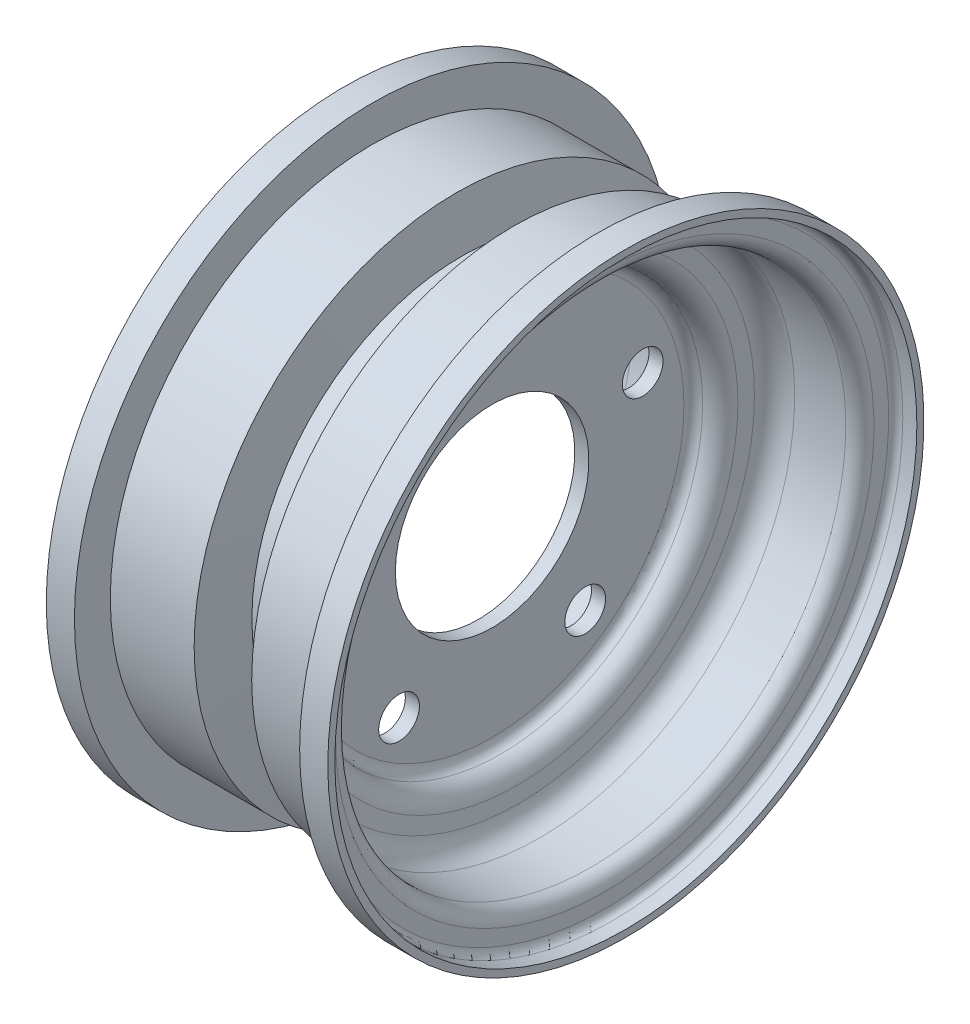
SolidWorks part; units mm, degrees
material "1023 Carbon Steel Sheet (SS)"
ref_plane "Front Plane" through (0, 0, 0) normal (0, 0, 1) x (1, 0, 0)
ref_plane "Top Plane" through (0, 0, 0) normal (0, 1, 0) x (1, 0, 0)
ref_plane "Right Plane" through (0, 0, 0) normal (1, 0, 0) x (0, 0, -1)
sketch "Sketch2" plane through (0, 0, 0) normal (0, 0, 1) x (1, 0, 0)
  line L0 (2.54, 0) -> (2.54, 34.925) construction
  line L1 (2.54, 34.925) -> (2.54, 73.025)
  line L2 (2.54, 73.025) -> (10.922, 73.025)
  line L3 (50.8, 107.569) -> (50.8, 105.029)
  line L4 (12.7, 92.075) -> (43.18, 92.075)
  line L5 (43.18, 92.075) -> (43.18, 105.029)
  line L6 (43.18, 105.029) -> (50.8, 105.029)
  line L7 (10.922, 73.025) -> (12.7, 92.075)
  line L8 (0, 0) -> (2.54, 0) construction
  line L9 (0, 0) -> (0, 213.5492) construction
  line L10 (0, 34.925) -> (0, 75.565)
  line L11 (0, 75.565) -> (8.608, 75.565)
  line L12 (8.608, 75.565) -> (10.386, 94.615)
  line L13 (10.386, 94.615) -> (40.64, 94.615)
  line L14 (40.64, 94.615) -> (40.64, 107.569)
  line L15 (40.64, 107.569) -> (48.26, 107.569)
  line L16 (48.26, 107.569) -> (48.26, 107.569)
  line L17 (0, 34.925) -> (2.54, 34.925)
  line L18 (48.26, 107.569) -> (50.8, 107.569)
  dimension "D1" = 34.925
  dimension "D2" = 38.1
  dimension "D3" = 8.382
  dimension "D4" = 19.05
  dimension "D5" = 2.54
  dimension "D6" = 7.62
  dimension "D7" = 30.48
  dimension "0.51" = 12.954
  dimension "D8" = 2.54
  dimension "D9" = 48.26
  dimension "D10" = 2.54
revolve "Revolve2" add sketch "Sketch2" angle 360 about L8 region at (1.27, 35.8114, 0)
mirror "Mirror1" about plane through (0, 0, 0) normal (1, 0, 0) of "Revolve2"
sketch "Sketch5" plane through (0, 0, 0) normal (1, 0, 0) x (0, 0, -1)
  line L1 (54.3529, 17.6603) -> (0, 57.15) construction
  line L2 (0, 57.15) -> (-54.3529, 17.6603) construction
  line L8 (-54.3529, 17.6603) -> (-33.5919, -46.2353) construction
  line L9 (-33.5919, -46.2353) -> (33.5919, -46.2353) construction
  line L10 (33.5919, -46.2353) -> (54.3529, 17.6603) construction
  circle A3 centre (0, 0) radius 57.15 construction
  point P2 (-34.925, 14.514)
  point P13 (0, 0)
  point P14 (0, 0)
  dimension "D1" = 114.3
hole_wizard "37/64 (0.57813) Diameter Hole1" positions "Sketch6" profile "Sketch7" hole size "37/64" standard "ANSI Inch" end condition through all
sketch "Sketch6" plane through (2.54, 0, 0) normal (1, 0, 0) x (0, 0, -1)
  point P0 (0, 57.15)
  point P3 (54.3529, 17.6603)
  point P6 (33.5919, -46.2353)
  point P9 (-33.5919, -46.2353)
  point P12 (-54.3529, 17.6603)
sketch "Sketch7" plane through (2.54, 57.15, 0) normal (0, 1, 0) x (0, 0, -1)
  line L0 (0, 0) -> (0, 53.34)
  line L1 (0, 53.34) -> (7.3423, 53.34)
  line L2 (7.3423, 53.34) -> (7.3423, 0)
  line L5 (7.3423, 0) -> (0, 0)
  line L11 (0, -6.35) -> (0, 107.95) construction
  dimension "Thru Hole Dia." = 14.6845
  dimension "Thru Hole Depth" = 53.34
fillet "Fillet1" radius 3.81 2 edges at (2.54, 0, 73.025) (-2.54, 0, 73.025)
fillet "Fillet2" radius 7.62 4 edges at (12.7, 0, 92.075) (10.922, 0, 73.025) (-12.7, 0, 92.075) (-10.922, 0, 73.025)
fillet "Fillet3" radius 5.08 2 edges at (43.18, 0, 92.075) (-43.18, 0, 92.075)
fillet "Fillet4" radius 2.54 2 edges at (43.18, 0, 105.029) (-43.18, 0, 105.029)
